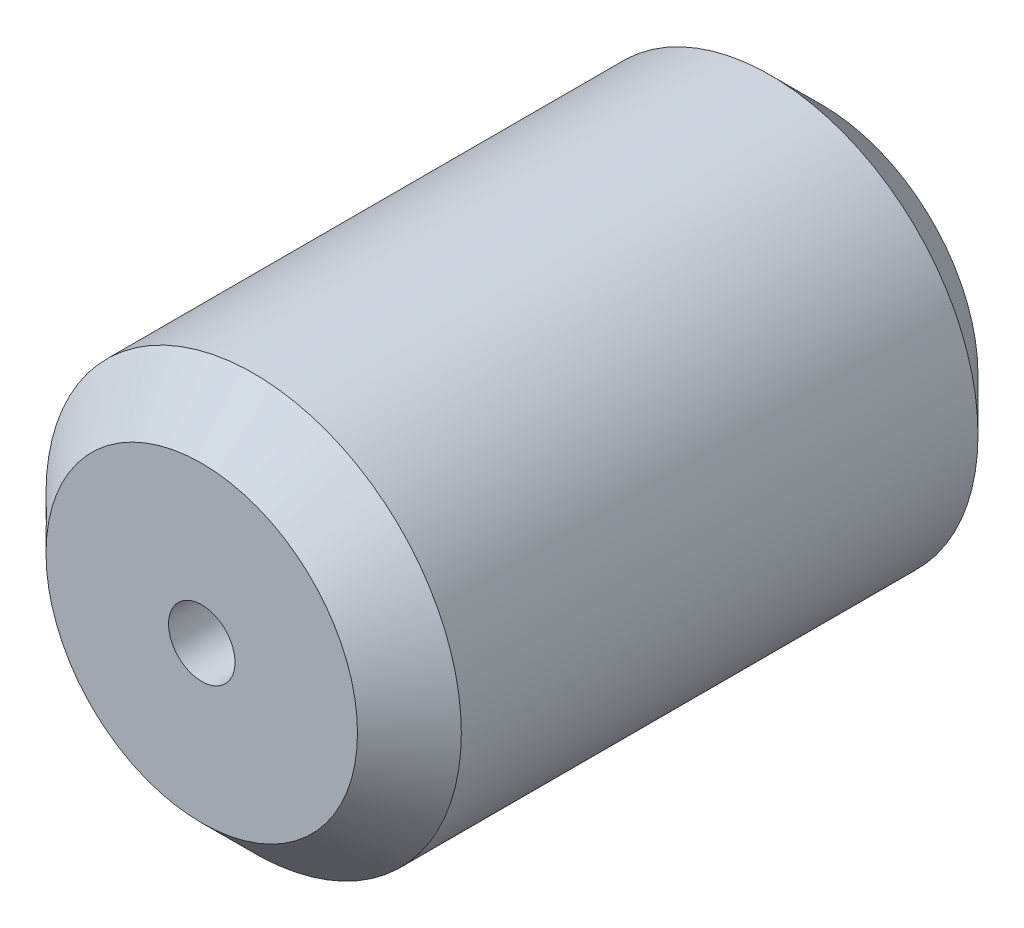
SolidWorks part; units mm, degrees
material "ALUMINUM 6061-T6; 6061-T651"
ref_plane "Front Plane" through (0, 0, 0) normal (0, 0, 1) x (1, 0, 0)
ref_plane "Top Plane" through (0, 0, 0) normal (0, 1, 0) x (1, 0, 0)
ref_plane "Right Plane" through (0, 0, 0) normal (1, 0, 0) x (0, 0, -1)
sketch "Sketch1" plane through (0, 0, 0) normal (0, 0, 1) x (1, 0, 0)
  circle A0 centre (0, 0) radius 6.35
  circle A1 centre (0, 0) radius 1.016
  dimension "D1" = 12.7
  dimension "D2" = 2.032
extrude "Boss-Extrude1" add sketch "Sketch1" along normal blind 9.4869 and the other way blind 9.4869
chamfer "Chamfer1" distance 1.5875 angle 45 2 edges at (6.35, 0, -9.4869) (6.35, 0, 9.4869)
